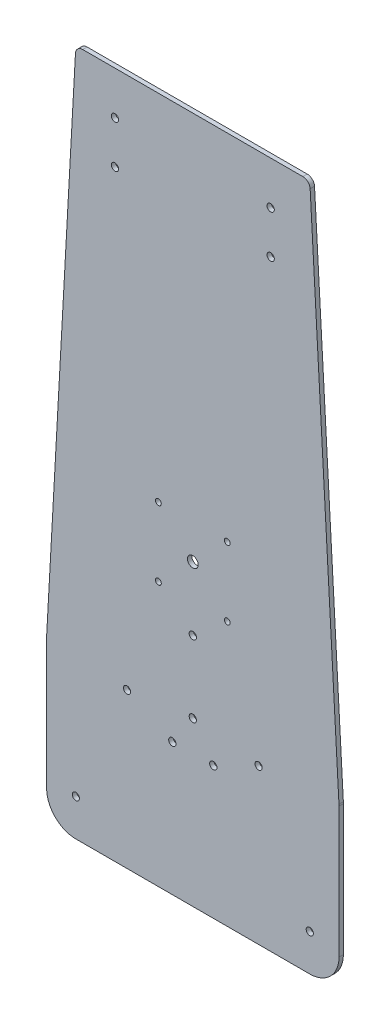
SolidWorks part; units mm, degrees
ref_plane "Alzado" through (0, 0, 0) normal (0, 0, 1) x (1, 0, 0)
ref_plane "Planta" through (0, 0, 0) normal (0, 1, 0) x (1, 0, 0)
ref_plane "Vista lateral" through (0, 0, 0) normal (1, 0, 0) x (0, 0, -1)
sketch "Croquis1" plane through (0, 0, 0) normal (0, 0, 1) x (1, 0, 0)
  line L0 (0, -28.2) -> (0, -108.2) construction
  line L1 (-23.57, -23.57) -> (23.57, -23.57) construction
  line L2 (-23.57, -23.57) -> (-23.57, 23.57) construction
  line L3 (-23.57, 23.57) -> (23.57, 23.57) construction
  line L4 (23.57, -23.57) -> (23.57, 23.57) construction
  line L5 (-23.57, -23.57) -> (23.57, 23.57) construction
  line L6 (-23.57, 23.57) -> (23.57, -23.57) construction
  line L7 (-28.2, -28.2) -> (28.2, -28.2) construction
  line L8 (-28.2, -28.2) -> (-28.2, 28.2) construction
  line L9 (-28.2, 28.2) -> (28.2, 28.2) construction
  line L10 (28.2, -28.2) -> (28.2, 28.2) construction
  line L11 (-28.2, -28.2) -> (28.2, 28.2) construction
  line L12 (-28.2, 28.2) -> (28.2, -28.2) construction
  line L13 (0, -28.2) -> (30.1, -28.2) construction
  line L14 (0, -108.2) -> (0, -169.2) construction
  line L15 (-30.1, -108.2) -> (30.1, -108.2) construction
  line L16 (-30.1, -108.2) -> (-30.1, -28.2) construction
  line L17 (-30.1, -28.2) -> (30.1, -28.2) construction
  line L18 (30.1, -108.2) -> (30.1, -28.2) construction
  line L19 (-30.1, -108.2) -> (30.1, -28.2) construction
  line L20 (-30.1, -28.2) -> (30.1, -108.2) construction
  line L21 (-14, -108.7) -> (-14, -113.7) construction
  line L22 (-221.5898, -108.7) -> (221.5898, -108.7) construction
  line L23 (-221.5898, -108.7) -> (-221.5898, -168.7) construction
  line L24 (-221.5898, -168.7) -> (221.5898, -168.7) construction
  line L25 (221.5898, -108.7) -> (221.5898, -168.7) construction
  line L26 (-221.5898, -108.7) -> (221.5898, -168.7) construction
  line L27 (-221.5898, -168.7) -> (221.5898, -108.7) construction
  line L28 (-221.5898, -122.2) -> (221.5898, -122.2) construction
  line L29 (-221.5898, -138.7) -> (221.5898, -138.7) construction
  line L30 (0, -169.2) -> (0, -204.2) construction
  line L31 (-100, -204.2) -> (100, -204.2)
  line L32 (100, -204.2) -> (100, -94.2)
  line L33 (100, -94.2) -> (80, 265.8)
  line L34 (80, 265.8) -> (-80, 265.8)
  line L35 (0, 265.8) -> (0, -169.2) construction
  line L36 (-100, -204.2) -> (-100, -94.2)
  line L37 (-100, -94.2) -> (-80, 265.8)
  line L38 (53.25, 221.8) -> (68.3, 221.8) construction
  line L39 (-53.25, 221.8) -> (-68.3, 221.8) construction
  line L40 (38.2, 191.75) -> (68.3, 191.75) construction
  line L41 (38.2, 191.75) -> (38.2, 251.85) construction
  line L42 (38.2, 251.85) -> (68.3, 251.85) construction
  line L43 (68.3, 191.75) -> (68.3, 251.85) construction
  line L44 (38.2, 191.75) -> (68.3, 251.85) construction
  line L45 (38.2, 251.85) -> (68.3, 191.75) construction
  line L46 (-38.2, 251.85) -> (-68.3, 191.75) construction
  line L47 (-38.2, 191.75) -> (-68.3, 251.85) construction
  line L48 (-38.2, 251.85) -> (-68.3, 251.85) construction
  line L49 (-38.2, 191.75) -> (-38.2, 251.85) construction
  line L50 (-38.2, 191.75) -> (-68.3, 191.75) construction
  line L51 (-68.3, 191.75) -> (-68.3, 251.85) construction
  circle A0 centre (-23.57, 23.57) radius 2
  circle A1 centre (23.57, 23.57) radius 2
  circle A2 centre (-23.57, -23.57) radius 2
  circle A3 centre (23.57, -23.57) radius 2
  circle A4 centre (0, 0) radius 3.675
  circle A5 centre (-14, -113.7) radius 6 construction
  circle A6 centre (14, -113.7) radius 6 construction
  circle A7 centre (-14, -113.7) radius 2.5
  circle A8 centre (14, -113.7) radius 2.5
  circle A9 centre (0, 0) radius 8 construction
  circle A10 centre (-45, -98.4) radius 12 construction
  circle A11 centre (-45, -98.4) radius 2.45
  circle A12 centre (45, -98.4) radius 12 construction
  circle A13 centre (45, -98.4) radius 2.45
  circle A14 centre (-80, -179) radius 12 construction
  circle A15 centre (-80, -179) radius 2.45
  circle A16 centre (80, -179) radius 2.45
  circle A17 centre (80, -179) radius 12 construction
  circle A18 centre (0, -43.7) radius 2.5
  circle A19 centre (0, -92.7) radius 2.5
  circle A20 centre (53.25, 236.35) radius 2.5
  circle A21 centre (53.25, 207.25) radius 2.5
  circle A22 centre (-53.25, 207.25) radius 2.5
  circle A23 centre (-53.25, 236.35) radius 2.5
  point P0 (0, 0)
  point P10 (0, 0)
  point P19 (0, -68.2)
  point P21 (0, -138.7)
  point P64 (53.25, 221.8)
  dimension "D3" = 4
  dimension "D4" = 4
  dimension "D5" = 4
  dimension "D6" = 4
  dimension "D9" = 7.35
  dimension "D16" = 12
  dimension "D17" = 5
  dimension "D18" = 16
  dimension "D19" = 10.3
  dimension "D20" = 24
  dimension "D22" = 4.9
  dimension "D24" = 24
  dimension "D25" = 4.9
  dimension "D32" = 5
  dimension "D33" = 5
  dimension "D41" = 5
  dimension "D1" = 47.14
  dimension "D2" = 47.14
  dimension "D7" = 56.4
  dimension "D8" = 56.4
  dimension "D10" = 80
  dimension "D11" = 30.1
  dimension "D12" = 61
  dimension "D13" = 13.5
  dimension "D14" = 14
  dimension "D15" = 5
  dimension "D21" = 45
  dimension "D23" = 10.3
  dimension "D26" = 80
  dimension "D27" = 100
  dimension "D28" = 35
  dimension "D29" = 110
  dimension "D30" = 80
  dimension "D31" = 470
  dimension "D34" = 15.5
  dimension "D35" = 15.5
  dimension "D36" = 25.05
  dimension "D37" = 60.1
  dimension "D38" = 30.1
  dimension "D39" = 15.5
  dimension "D40" = 15.05
  dimension "D42" = 250
extrude "Saliente-Extruir1" add sketch "Croquis1" along normal blind 3
fillet "Redondeo1" radius 20 2 edges at (-100, -204.2, 1.5) (100, -204.2, 1.5)
fillet "Redondeo2" radius 20 2 edges at (100, -94.2, 1.5) (-100, -94.2, 1.5)
fillet "Redondeo3" radius 5 2 edges at (80, 265.8, 1.5) (-80, 265.8, 1.5)
